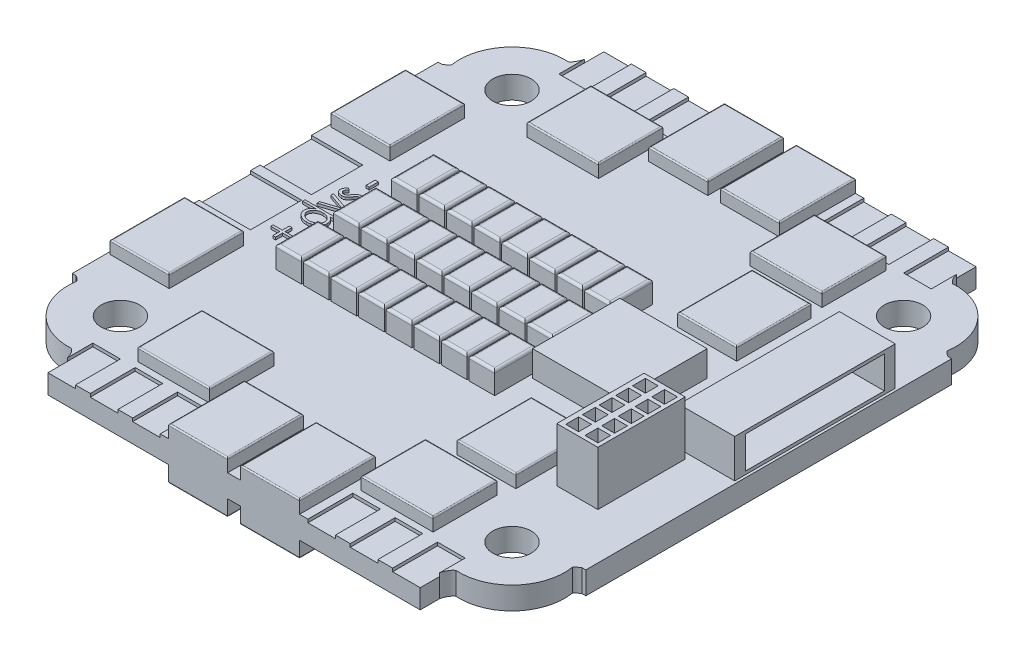
SolidWorks part; units mm, degrees
ref_plane "Ön Düzlem" through (0, 0, 0) normal (0, 0, 1) x (1, 0, 0)
ref_plane "Üst Düzlem" through (0, 0, 0) normal (0, 1, 0) x (1, 0, 0)
ref_plane "Sağ Düzlem" through (0, 0, 0) normal (1, 0, 0) x (0, 0, -1)
sketch "Çizim1" plane through (0, 0, 0) normal (0, 1, 0) x (1, 0, 0)
  line L0 (0, 44.0782) -> (0, -46.2011) construction
  line L1 (20, -21.65) -> (-20, -21.65)
  line L2 (20, -21.65) -> (20, 21.65)
  line L3 (20, 21.65) -> (-20, 21.65)
  line L4 (-20, -21.65) -> (-20, 21.65)
  line L5 (20, -21.65) -> (-20, 21.65) construction
  line L6 (20, 21.65) -> (-20, -21.65) construction
  line L7 (-44.1341, 0) -> (49.6089, 0) construction
  line L9 (15.25, -15.25) -> (-15.25, -15.25) construction
  line L10 (15.25, -15.25) -> (15.25, 15.25) construction
  line L11 (15.25, 15.25) -> (-15.25, 15.25) construction
  line L12 (-15.25, -15.25) -> (-15.25, 15.25) construction
  line L13 (15.25, -15.25) -> (-15.25, 15.25) construction
  line L14 (15.25, 15.25) -> (-15.25, -15.25) construction
  point P0 (0, 0)
  point P10 (0, 0)
  dimension "D1" = 40
  dimension "D2" = 43.3
  dimension "D3" = 30.5
  dimension "D4" = 30.5
extrude "Yükseklik-Ekstrüzyon1" add sketch "Çizim1" along normal blind 1.75
sketch "Çizim2" plane through (0, 0, 0) normal (0, 1, 0) x (1, 0, 0)
  line L1 (15.25, -15.25) -> (-15.25, -15.25) construction
  line L2 (15.25, -15.25) -> (15.25, 15.25) construction
  line L3 (15.25, 15.25) -> (-15.25, 15.25) construction
  line L4 (-15.25, -15.25) -> (-15.25, 15.25) construction
  line L5 (15.25, -15.25) -> (-15.25, 15.25) construction
  line L6 (15.25, 15.25) -> (-15.25, -15.25) construction
  circle A0 centre (-15.25, 15.25) radius 1.5
  circle A1 centre (15.25, 15.25) radius 1.5
  circle A2 centre (15.25, -15.25) radius 1.5
  circle A3 centre (-15.25, -15.25) radius 1.5
  point P0 (0, 0)
  dimension "D1" = 30.5
  dimension "D2" = 30.5
extrude "Kes-Ekstrüzyon1" cut sketch "Çizim2" along normal blind 1.75
sketch "Çizim3" plane through (0, 0, 0) normal (0, 1, 0) x (1, 0, 0)
  line L0 (-19.297, 14.593) -> (-19.4339, 14.3985) construction
  line L1 (-19.4339, 14.3985) -> (-19.7178, 14.25) construction
  line L2 (-20, 21.65) -> (-20, -21.65) construction
  line L3 (-19.7178, 14.25) -> (-20, 14.25)
  line L4 (-20, 21.65) -> (-20, 13.5542) construction
  line L5 (-20, 14.25) -> (-20, 21.65)
  line L6 (-20, 21.65) -> (-14.5, 21.65)
  line L7 (20, 21.65) -> (-20, 21.65) construction
  line L8 (-14.5, 21.65) -> (-14.5, 20.1378)
  line L9 (-14.9713, 19.3405) -> (-14.7537, 19.4813) construction
  line L10 (-14.7537, 19.4813) -> (-14.5714, 19.809) construction
  line L11 (-14.5714, 19.809) -> (-14.5, 20.1378) construction
  line L12 (20, 21.65) -> (14.5, 21.65)
  line L13 (14.5, 21.65) -> (14.5, 20.1378)
  line L14 (14.9713, 19.3405) -> (14.7537, 19.4813) construction
  line L15 (0, 29.2521) -> (0, -30.7082) construction
  line L16 (-36.8808, 0) -> (40.0068, 0) construction
  line L17 (14.7537, 19.4813) -> (14.5714, 19.809) construction
  line L18 (14.5714, 19.809) -> (14.5, 20.1378) construction
  line L19 (20, 14.25) -> (20, 21.65)
  line L20 (19.7178, 14.25) -> (20, 14.25)
  line L21 (19.297, 14.593) -> (19.4339, 14.3985) construction
  line L22 (19.4339, 14.3985) -> (19.7178, 14.25) construction
  line L23 (14.9713, -19.3405) -> (14.7537, -19.4813) construction
  line L24 (14.7537, -19.4813) -> (14.5714, -19.809) construction
  line L25 (14.5714, -19.809) -> (14.5, -20.1378) construction
  line L26 (19.297, -14.593) -> (19.4339, -14.3985) construction
  line L27 (19.4339, -14.3985) -> (19.7178, -14.25) construction
  line L28 (19.7178, -14.25) -> (20, -14.25)
  line L29 (20, -14.25) -> (20, -21.65)
  line L30 (20, -21.65) -> (14.5, -21.65)
  line L31 (14.5, 18.3234) -> (-14.5, 18.3234) construction
  line L32 (14.5, -21.65) -> (14.5, -20.1378)
  line L33 (14.5, 18.3234) -> (14.5, 24.9766) construction
  line L34 (-20, -21.65) -> (-14.5, -21.65)
  line L35 (-14.5, -21.65) -> (-14.5, -20.1378)
  line L36 (-14.9713, -19.3405) -> (-14.7537, -19.4813) construction
  line L37 (-14.7537, -19.4813) -> (-14.5714, -19.809) construction
  line L38 (-14.5714, -19.809) -> (-14.5, -20.1378) construction
  line L39 (-20, -14.25) -> (-20, -21.65)
  line L40 (-19.7178, -14.25) -> (-20, -14.25)
  line L41 (-19.297, -14.593) -> (-19.4339, -14.3985) construction
  line L42 (-19.4339, -14.3985) -> (-19.7178, -14.25) construction
  line L48 (14.5, 24.9766) -> (-14.5, 24.9766) construction
  line L49 (-14.5, 18.3234) -> (-14.5, 24.9766) construction
  line L50 (14.5, 18.3234) -> (-14.5, 24.9766) construction
  line L51 (14.5, 24.9766) -> (-14.5, 18.3234) construction
  line L52 (-14.1712, -14.25) -> (-25.8288, -14.25) construction
  line L53 (-14.1712, -14.25) -> (-14.1712, 14.25) construction
  line L54 (-14.1712, 14.25) -> (-25.8288, 14.25) construction
  line L55 (-25.8288, -14.25) -> (-25.8288, 14.25) construction
  line L56 (-14.1712, -14.25) -> (-25.8288, 14.25) construction
  line L57 (-14.1712, 14.25) -> (-25.8288, -14.25) construction
  arc A0 (14.9713, 19.3405) -> (19.297, 14.593) centre (15.25, 15.25) cw
  circle A1 centre (0, 0) radius 6.746 construction
  arc A2 (14.9713, -19.3405) -> (19.297, -14.593) centre (15.25, -15.25) ccw
  arc A3 (-14.9713, -19.3405) -> (-19.297, -14.593) centre (-15.25, -15.25) cw
  arc A5 (-14.9713, 19.3405) -> (-19.297, 14.593) centre (-15.25, 15.25) ccw
  spline S0 degree 2 poles (-19.297, 14.593) (-19.4339, 14.3985) (-19.7178, 14.25) knots 0 0 0 1 1 1
  spline S1 degree 3 poles (-14.9713, 19.3405) (-14.7537, 19.4813) (-14.5714, 19.809) (-14.5, 20.1378) knots 0 0 0 0 1 1 1 1
  spline S2 degree 3 poles (14.9713, 19.3405) (14.7537, 19.4813) (14.5714, 19.809) (14.5, 20.1378) knots 0 0 0 0 1 1 1 1
  spline S3 degree 2 poles (19.297, 14.593) (19.4339, 14.3985) (19.7178, 14.25) knots 0 0 0 1 1 1
  spline S4 degree 3 poles (14.9713, -19.3405) (14.7537, -19.4813) (14.5714, -19.809) (14.5, -20.1378) knots 0 0 0 0 1 1 1 1
  spline S5 degree 2 poles (19.297, -14.593) (19.4339, -14.3985) (19.7178, -14.25) knots 0 0 0 1 1 1
  spline S6 degree 3 poles (-14.9713, -19.3405) (-14.7537, -19.4813) (-14.5714, -19.809) (-14.5, -20.1378) knots 0 0 0 0 1 1 1 1
  spline S7 degree 2 poles (-19.297, -14.593) (-19.4339, -14.3985) (-19.7178, -14.25) knots 0 0 0 1 1 1
  point P43 (0, 21.65)
  point P61 (-20, 0)
  dimension "D1" = 29
  dimension "D2" = 28.5
extrude "Kes-Ekstrüzyon4" cut sketch "Çizim3" along normal blind 1.75
sketch "Çizim5" plane through (0, 0, 0) normal (0, 1, 0) x (1, 0, 0)
  line L0 (0, 30.9186) -> (0, -32.6939) construction
  line L1 (-49.0396, 0) -> (40.1136, 0) construction
  line L2 (-10.125, 21.65) -> (-10.125, 17.2464) construction
  line L3 (-14.5, 21.65) -> (-5.75, 21.65) construction
  line L4 (-14.5, 21.65) -> (-14.5, 18.15) construction
  line L5 (-14.5, 18.15) -> (-5.75, 18.15) construction
  line L6 (-5.75, 21.65) -> (-5.75, 18.15) construction
  line L7 (-14.5, 21.65) -> (-12.3523, 21.65)
  line L8 (-14.5, 21.65) -> (-14.5, 18.15)
  line L9 (-14.5, 18.15) -> (-12.3523, 18.15)
  line L10 (-12.3523, 21.65) -> (-12.3523, 18.15)
  line L11 (-5.75, 18.15) -> (-7.8977, 18.15)
  line L12 (-5.75, 21.65) -> (-5.75, 18.15)
  line L13 (-5.75, 21.65) -> (-7.8977, 21.65)
  line L14 (-7.8977, 21.65) -> (-7.8977, 18.15)
  line L15 (-5.75, 19.9) -> (-14.5, 19.9) construction
  line L16 (9.05, 21.65) -> (11.2, 18.15) construction
  line L17 (-9.05, 18.15) -> (-11.2, 18.15)
  line L18 (-9.05, 18.15) -> (-9.05, 21.65)
  line L19 (-9.05, 21.65) -> (-11.2, 21.65)
  line L20 (-11.2, 18.15) -> (-11.2, 21.65)
  line L21 (-9.05, 18.15) -> (-11.2, 21.65) construction
  line L22 (-9.05, 21.65) -> (-11.2, 18.15) construction
  line L23 (9.05, 18.15) -> (11.2, 21.65) construction
  line L24 (5.75, 19.9) -> (14.5, 19.9) construction
  line L25 (5.75, 21.65) -> (5.75, 18.15) construction
  line L26 (14.5, 18.15) -> (5.75, 18.15) construction
  line L27 (14.5, 21.65) -> (14.5, 18.15) construction
  line L28 (14.5, 21.65) -> (5.75, 21.65) construction
  line L29 (10.125, 21.65) -> (10.125, 17.2464) construction
  line L30 (11.2, 18.15) -> (11.2, 21.65)
  line L31 (9.05, 21.65) -> (11.2, 21.65)
  line L32 (9.05, 18.15) -> (9.05, 21.65)
  line L33 (9.05, 18.15) -> (11.2, 18.15)
  line L34 (7.8977, 21.65) -> (7.8977, 18.15)
  line L35 (5.75, 21.65) -> (7.8977, 21.65)
  line L36 (5.75, 21.65) -> (5.75, 18.15)
  line L37 (5.75, 18.15) -> (7.8977, 18.15)
  line L38 (12.3523, 21.65) -> (12.3523, 18.15)
  line L39 (14.5, 18.15) -> (12.3523, 18.15)
  line L40 (14.5, 21.65) -> (14.5, 18.15)
  line L41 (14.5, 21.65) -> (12.3523, 21.65)
  line L42 (10.125, -21.65) -> (10.125, -17.2464) construction
  line L43 (14.5, -21.65) -> (5.75, -21.65) construction
  line L44 (14.5, -21.65) -> (14.5, -18.15) construction
  line L45 (14.5, -18.15) -> (5.75, -18.15) construction
  line L46 (5.75, -21.65) -> (5.75, -18.15) construction
  line L47 (5.75, -19.9) -> (14.5, -19.9) construction
  line L48 (9.05, -18.15) -> (11.2, -21.65) construction
  line L49 (-9.05, -21.65) -> (-11.2, -18.15) construction
  line L50 (-9.05, -18.15) -> (-11.2, -21.65) construction
  line L51 (9.05, -21.65) -> (11.2, -18.15) construction
  line L52 (-5.75, -19.9) -> (-14.5, -19.9) construction
  line L53 (-5.75, -21.65) -> (-5.75, -18.15) construction
  line L54 (-14.5, -18.15) -> (-5.75, -18.15) construction
  line L55 (-14.5, -21.65) -> (-14.5, -18.15) construction
  line L56 (-14.5, -21.65) -> (-5.75, -21.65) construction
  line L57 (-10.125, -21.65) -> (-10.125, -17.2464) construction
  line L58 (14.5, -21.65) -> (12.3523, -21.65)
  line L59 (14.5, -21.65) -> (14.5, -18.15)
  line L60 (14.5, -18.15) -> (12.3523, -18.15)
  line L61 (12.3523, -21.65) -> (12.3523, -18.15)
  line L62 (5.75, -18.15) -> (7.8977, -18.15)
  line L63 (5.75, -21.65) -> (5.75, -18.15)
  line L64 (5.75, -21.65) -> (7.8977, -21.65)
  line L65 (7.8977, -21.65) -> (7.8977, -18.15)
  line L66 (9.05, -18.15) -> (11.2, -18.15)
  line L67 (9.05, -18.15) -> (9.05, -21.65)
  line L68 (9.05, -21.65) -> (11.2, -21.65)
  line L69 (11.2, -18.15) -> (11.2, -21.65)
  line L70 (-11.2, -18.15) -> (-11.2, -21.65)
  line L71 (-9.05, -21.65) -> (-11.2, -21.65)
  line L72 (-9.05, -18.15) -> (-9.05, -21.65)
  line L73 (-9.05, -18.15) -> (-11.2, -18.15)
  line L74 (-7.8977, -21.65) -> (-7.8977, -18.15)
  line L75 (-5.75, -21.65) -> (-7.8977, -21.65)
  line L76 (-5.75, -21.65) -> (-5.75, -18.15)
  line L77 (-5.75, -18.15) -> (-7.8977, -18.15)
  line L78 (-12.3523, -21.65) -> (-12.3523, -18.15)
  line L79 (-14.5, -18.15) -> (-12.3523, -18.15)
  line L80 (-14.5, -21.65) -> (-14.5, -18.15)
  line L81 (-14.5, -21.65) -> (-12.3523, -21.65)
  point P18 (-10.125, 19.9)
  point P39 (10.125, 19.9)
  point P72 (10.125, -19.9)
  point P73 (-10.125, -19.9)
  dimension "D1" = 8.75
  dimension "D2" = 3.5
  dimension "D3" = 2.15
extrude "Kes-Ekstrüzyon5" cut sketch "Çizim5" along normal blind 1 from offset 1.5
sketch "Çizim6" plane through (0, 0, 0) normal (0, 1, 0) x (1, 0, 0)
  line L0 (-37.3382, 0) -> (45.0839, 0) construction
  line L1 (-20, 14.25) -> (-20, -14.25) construction
  line L2 (-15.9, -4.375) -> (-20, -4.375) construction
  line L3 (-15.9, -4.375) -> (-15.9, 4.375) construction
  line L4 (-15.9, 4.375) -> (-20, 4.375) construction
  line L5 (-20, -4.375) -> (-20, 4.375) construction
  line L6 (-15.9, -4.375) -> (-20, 4.375) construction
  line L7 (-15.9, 4.375) -> (-20, -4.375) construction
  line L8 (-20, -4.375) -> (-20, -0.375)
  line L9 (-20, 4.375) -> (-16, 4.375)
  line L10 (-20, 4.375) -> (-20, 0.375)
  line L11 (-20, 0.375) -> (-16, 0.375)
  line L12 (-16, 4.375) -> (-16, 0.375)
  line L13 (-20, -4.375) -> (-16, -4.375)
  line L14 (-16, -4.375) -> (-16, -0.375)
  line L15 (-20, -0.375) -> (-16, -0.375)
  point P3 (-17.95, 0)
  dimension "D1" = 8.75
  dimension "D2" = 4.1
  dimension "D3" = 4
  dimension "D4" = 4
extrude "Kes-Ekstrüzyon7" cut sketch "Çizim6" along normal blind 1 from offset 1.5
sketch "Çizim7" plane through (0, 0, 0) normal (0, 1, 0) x (1, 0, 0)
  line L0 (12, 0) -> (-20, 0) construction
  line L1 (-20, 14.25) -> (-20, 4.375) construction
  line L2 (-15.2, -11.5) -> (-20, -11.5) construction
  line L3 (-15.2, -11.5) -> (-15.2, 11.5) construction
  line L4 (-15.2, 11.5) -> (-20, 11.5) construction
  line L5 (-20, -11.5) -> (-20, 11.5) construction
  line L6 (-15.2, -11.5) -> (-20, 11.5) construction
  line L7 (-15.2, 11.5) -> (-20, -11.5) construction
  line L8 (-19.8, 11.9264) -> (-19.8, -13.8708) construction
  line L9 (-19.8, -11.5) -> (-15.2, -11.5)
  line L10 (-19.8, 11.5) -> (-15.2, 11.5)
  line L11 (-19.8, 11.5) -> (-19.8, 5.7)
  line L12 (-19.8, 5.7) -> (-15.2, 5.7)
  line L13 (-15.2, 11.5) -> (-15.2, 5.7)
  line L14 (-15.2, -11.5) -> (-15.2, -5.7)
  line L15 (-19.8, -11.5) -> (-19.8, -5.7)
  line L16 (-19.8, -5.7) -> (-15.2, -5.7)
  line L17 (12, 23.8694) -> (12, -27.9826) construction
  line L18 (20, -14.25) -> (20, 14.25) construction
  line L19 (-20, 21.0492) -> (-20, -26.7007) construction
  line L20 (-4, 16.02) -> (-4, -18.6893) construction
  line L21 (11.8, -11.5) -> (11.8, -5.7)
  line L22 (11.8, -11.5) -> (7.2, -11.5)
  line L23 (7.2, -11.5) -> (7.2, -5.7)
  line L24 (11.8, -5.7) -> (7.2, -5.7)
  line L25 (11.8, 11.5) -> (11.8, 5.7)
  line L26 (11.8, 5.7) -> (7.2, 5.7)
  line L27 (7.2, 11.5) -> (7.2, 5.7)
  line L28 (11.8, 11.5) -> (7.2, 11.5)
  point P3 (-17.6, 0)
  point P16 (-17.5, -11.5)
  point P19 (-17.5, -5.7)
  dimension "D1" = 23
  dimension "D2" = 0.2
  dimension "D3" = 5.8
  dimension "D4" = 8
extrude "Yükseklik-Ekstrüzyon2" add sketch "Çizim7" along normal blind 2.75 and the other way blind 1.25
sketch "Çizim9" plane through (0, 0, 0) normal (0, 1, 0) x (1, 0, 0)
  line L0 (11.8, 15.4181) -> (11.8, -15.0147) construction
  line L1 (-13.0732, 0) -> (28.7719, 0) construction
  line L2 (-13.0732, 3.4) -> (30.1552, 3.4) construction
  line L4 (11.8, 3.4) -> (5, 3.4)
  line L5 (11.8, 3.4) -> (11.8, -3.4)
  line L6 (11.8, -3.4) -> (5, -3.4)
  line L7 (5, 3.4) -> (5, -3.4)
  dimension "D1" = 3.4
  dimension "D2" = 6.8
  dimension "D3" = 6.8
extrude "Yükseklik-Ekstrüzyon3" add sketch "Çizim9" along normal blind 3.75
sketch "Çizim10" plane through (0, 0, 0) normal (0, 1, 0) x (1, 0, 0)
  line L0 (0, 23.2569) -> (0, -24.4096) construction
  line L1 (5.75, 21.65) -> (-5.75, 21.65) construction
  line L2 (5.1, 15.75) -> (-5.1, 15.75) construction
  line L3 (5.1, 15.75) -> (5.1, 21.65) construction
  line L4 (5.1, 21.65) -> (-5.1, 21.65) construction
  line L5 (-5.1, 15.75) -> (-5.1, 21.65) construction
  line L6 (5.1, 15.75) -> (-5.1, 21.65) construction
  line L7 (5.1, 21.65) -> (-5.1, 15.75) construction
  line L8 (-5.1, 15.75) -> (-0.5021, 15.75)
  line L9 (5.1, 21.65) -> (0.5021, 21.65)
  line L10 (5.1, 21.65) -> (5.1, 15.75)
  line L11 (5.1, 15.75) -> (0.5021, 15.75)
  line L12 (0.5021, 21.65) -> (0.5021, 15.75)
  line L13 (-0.5021, 21.65) -> (-0.5021, 15.75)
  line L14 (-5.1, 21.65) -> (-0.5021, 21.65)
  line L15 (-5.1, 21.65) -> (-5.1, 15.75)
  line L16 (-34.7799, 0) -> (34.025, 0) construction
  line L17 (-17.6922, 17.65) -> (20.1896, 17.65) construction
  line L18 (-12.3523, 18.15) -> (-14.5, 18.15) construction
  line L19 (-17.6922, 15.15) -> (18.3088, 15.15) construction
  line L20 (11.5, 17.65) -> (11.5, 12.65)
  line L21 (11.5, 12.65) -> (-11.5, 12.65) construction
  line L22 (11.5, 12.65) -> (11.5, 17.65) construction
  line L23 (11.5, 17.65) -> (-11.5, 17.65) construction
  line L24 (-11.5, 12.65) -> (-11.5, 17.65) construction
  line L25 (11.5, 12.65) -> (-11.5, 17.65) construction
  line L26 (11.5, 17.65) -> (-11.5, 12.65) construction
  line L27 (-11.5, 17.65) -> (-5.9038, 17.65)
  line L28 (-11.5, 17.65) -> (-11.5, 12.65)
  line L29 (-11.5, 12.65) -> (-5.9038, 12.65)
  line L30 (-5.9038, 17.65) -> (-5.9038, 12.65)
  line L31 (11.5, 17.65) -> (5.9038, 17.65)
  line L32 (5.9038, 17.65) -> (5.9038, 12.65)
  line L33 (11.5, 12.65) -> (5.9038, 12.65)
  line L34 (11.5, -17.65) -> (-11.5, -12.65) construction
  line L35 (11.5, -12.65) -> (-11.5, -17.65) construction
  line L36 (-11.5, -12.65) -> (-11.5, -17.65) construction
  line L37 (11.5, -17.65) -> (-11.5, -17.65) construction
  line L38 (11.5, -12.65) -> (11.5, -17.65) construction
  line L39 (11.5, -12.65) -> (-11.5, -12.65) construction
  line L40 (-17.6922, -15.15) -> (18.3088, -15.15) construction
  line L41 (-17.6922, -17.65) -> (20.1896, -17.65) construction
  line L42 (5.1, -21.65) -> (-5.1, -15.75) construction
  line L43 (5.1, -15.75) -> (-5.1, -21.65) construction
  line L44 (-5.1, -15.75) -> (-5.1, -21.65) construction
  line L45 (5.1, -21.65) -> (-5.1, -21.65) construction
  line L46 (5.1, -15.75) -> (5.1, -21.65) construction
  line L47 (5.1, -15.75) -> (-5.1, -15.75) construction
  line L48 (0, -23.2569) -> (0, 24.4096) construction
  line L49 (11.5, -12.65) -> (5.9038, -12.65)
  line L50 (5.9038, -17.65) -> (5.9038, -12.65)
  line L51 (11.5, -17.65) -> (5.9038, -17.65)
  line L52 (-5.9038, -17.65) -> (-5.9038, -12.65)
  line L53 (-11.5, -12.65) -> (-5.9038, -12.65)
  line L54 (-11.5, -17.65) -> (-11.5, -12.65)
  line L55 (-11.5, -17.65) -> (-5.9038, -17.65)
  line L56 (11.5, -17.65) -> (11.5, -12.65)
  line L57 (-5.1, -21.65) -> (-5.1, -15.75)
  line L58 (-5.1, -21.65) -> (-0.5021, -21.65)
  line L59 (-0.5021, -21.65) -> (-0.5021, -15.75)
  line L60 (0.5021, -21.65) -> (0.5021, -15.75)
  line L61 (5.1, -15.75) -> (0.5021, -15.75)
  line L62 (5.1, -21.65) -> (5.1, -15.75)
  line L63 (5.1, -21.65) -> (0.5021, -21.65)
  line L64 (-5.1, -15.75) -> (-0.5021, -15.75)
  line L65 (-5.7307, 22.4988) -> (4.1432, 22.4988) construction
  point P3 (0, 18.7)
  point P22 (0, 15.15)
  point P53 (0, -15.15)
  point P54 (0, -18.7)
  dimension "D1" = 10.2
  dimension "D2" = 5.9
  dimension "D3" = 0.5
  dimension "D4" = 2.5
  dimension "D5" = 23
  dimension "D6" = 5.5962
  dimension "D7" = 0.8488
extrude "Yükseklik-Ekstrüzyon4" add sketch "Çizim10" along normal blind 2.75 and the other way blind 1.25
sketch "Çizim11" plane through (0, 0, 0) normal (0, 1, 0) x (1, 0, 0)
  line L0 (-37.3419, -0.2797) -> (45.0802, -0.2797) construction
  line L1 (-15.9037, -4.6547) -> (-20.0037, -4.6547) construction
  line L2 (-15.9037, -4.6547) -> (-15.9037, 4.0953) construction
  line L3 (-15.9037, 4.0953) -> (-20.0037, 4.0953) construction
  line L4 (-20.0037, -4.6547) -> (-20.0037, 4.0953) construction
  line L5 (-15.9037, -4.6547) -> (-20.0037, 4.0953) construction
  line L6 (-15.9037, 4.0953) -> (-20.0037, -4.6547) construction
  line L7 (-20.0037, -4.6547) -> (-20.0037, -0.6547)
  line L8 (-20.0037, 4.0953) -> (-16.0037, 4.0953)
  line L9 (-20.0037, 4.0953) -> (-20.0037, 0.0953)
  line L10 (-20.0037, 0.0953) -> (-16.0037, 0.0953)
  line L11 (-16.0037, 4.0953) -> (-16.0037, 0.0953)
  line L12 (-20.0037, -4.6547) -> (-16.0037, -4.6547)
  line L13 (-16.0037, -4.6547) -> (-16.0037, -0.6547)
  line L14 (-20.0037, -0.6547) -> (-16.0037, -0.6547)
  point P2 (-17.9537, -0.2797)
  dimension "D1" = 8.75
  dimension "D2" = 4.1
  dimension "D3" = 4
  dimension "D4" = 4
extrude "Kes-Ekstrüzyon8" cut sketch "Çizim11" along normal blind 0.5
sketch "Çizim12" plane through (0, 0, 0) normal (0, 1, 0) x (1, 0, 0)
  line L0 (20, 14.25) -> (29.4504, 14.25) construction
  line L1 (32.1594, 10.05) -> (-8.1295, 10.05) construction
  line L2 (19.8, 11.0054) -> (19.8, -21.7671) construction
  line L3 (20, -14.25) -> (20, 14.25) construction
  line L5 (19.8, 10.05) -> (15.45, 10.05)
  line L6 (19.8, 10.05) -> (19.8, -2.45)
  line L7 (19.8, -2.45) -> (15.45, -2.45)
  line L8 (15.45, 10.05) -> (15.45, -2.45)
  dimension "D1" = 4.2
  dimension "D2" = 0.2
  dimension "D3" = 12.5
  dimension "D4" = 4.35
extrude "Yükseklik-Ekstrüzyon5" add sketch "Çizim12" along normal blind 3 from surface starting at face at (-1.6364, 1.75, 0)
ref_plane "Düzlem1" through (29.8, 0, 0) normal (1, 0, 0) x (0, 0, -1)
sketch "Çizim13" plane through (29.8, 0, 0) normal (1, 0, 0) x (0, 0, -1)
  line L0 (3.8, 4.75) -> (3.8, 1.086) construction
  line L1 (10.05, 4.75) -> (-2.45, 4.75) construction
  line L2 (-2.45, 3.25) -> (10.05, 3.25) construction
  line L3 (-2.45, 4.75) -> (-2.45, 1.75) construction
  line L4 (10.05, 4.75) -> (10.05, 1.75) construction
  line L6 (9.2, 2) -> (-1.6, 2)
  line L7 (9.2, 2) -> (9.2, 4.5)
  line L8 (9.2, 4.5) -> (-1.6, 4.5)
  line L9 (-1.6, 2) -> (-1.6, 4.5)
  line L10 (9.2, 2) -> (-1.6, 4.5) construction
  line L11 (9.2, 4.5) -> (-1.6, 2) construction
  point P10 (3.8, 3.25)
  dimension "D1" = 10.8
  dimension "D2" = 2.5
extrude "Kes-Ekstrüzyon9" cut sketch "Çizim13" against normal blind 13
sketch "Çizim14" plane through (0, 0, 0) normal (0, 1, 0) x (1, 0, 0)
  line L0 (16.4, 0.4899) -> (16.4, -23.3722) construction
  line L1 (20, -14.25) -> (20, 14.25) construction
  line L2 (20, -2.9107) -> (10.3037, -2.9107) construction
  line L4 (16.4, -2.9107) -> (13.2, -2.9107)
  line L5 (16.4, -2.9107) -> (16.4, -9.7107)
  line L6 (16.4, -9.7107) -> (13.2, -9.7107)
  line L7 (13.2, -2.9107) -> (13.2, -9.7107)
  dimension "D1" = 3.6
  dimension "D2" = 3.2
  dimension "D3" = 6.8
extrude "Yükseklik-Ekstrüzyon6" add sketch "Çizim14" along normal blind 4.2 from surface starting at face at (17.625, 1.75, -3.8)
ref_plane "Düzlem2" through (0, 5.95, 0) normal (0, 1, 0) x (1, 0, 0)
sketch "Çizim15" plane through (0, 5.95, 0) normal (0, 1, 0) x (1, 0, 0)
  line L0 (14.8, -2.9107) -> (14.8, -11.4983) construction
  line L1 (13.2, -2.9107) -> (16.4, -2.9107) construction
  line L2 (13.2, -6.3107) -> (18.1949, -6.3107) construction
  line L3 (13.2, -9.7107) -> (13.2, -2.9107) construction
  line L4 (17.215, -3.2107) -> (12.1271, -3.2107) construction
  line L5 (13.2, -2.9107) -> (16.4, -2.9107) construction
  line L6 (14.8, -2.9107) -> (16.4, -2.9107) construction
  line L7 (15.6, -2.9107) -> (15.6, -10.0902) construction
  line L8 (15.1, -2.7946) -> (15.1, -11.569) construction
  line L9 (16.1, -2.7946) -> (16.1, -11.569) construction
  line L10 (13.6, -4.213) -> (14.6, -4.213)
  line L11 (15.1, -3.2107) -> (16.1, -3.2107)
  line L12 (15.1, -3.2107) -> (15.1, -4.213)
  line L13 (15.1, -4.213) -> (16.1, -4.213)
  line L14 (16.1, -3.2107) -> (16.1, -4.213)
  line L15 (14.6, -3.2107) -> (14.6, -4.213)
  line L16 (13.6, -3.2107) -> (14.6, -3.2107)
  line L17 (13.6, -3.2107) -> (13.6, -4.213)
  line L18 (13.6, -5.513) -> (14.6, -5.513)
  line L19 (14.6, -4.5107) -> (14.6, -5.513)
  line L20 (13.6, -4.5107) -> (14.6, -4.5107)
  line L21 (13.6, -4.5107) -> (13.6, -5.513)
  line L22 (13.6, -6.813) -> (14.6, -6.813)
  line L23 (14.6, -5.8107) -> (14.6, -6.813)
  line L24 (13.6, -5.8107) -> (14.6, -5.8107)
  line L25 (13.6, -5.8107) -> (13.6, -6.813)
  line L26 (13.6, -8.113) -> (14.6, -8.113)
  line L27 (14.6, -7.1107) -> (14.6, -8.113)
  line L28 (13.6, -7.1107) -> (14.6, -7.1107)
  line L29 (13.6, -7.1107) -> (13.6, -8.113)
  line L30 (13.6, -9.413) -> (14.6, -9.413)
  line L31 (14.6, -8.4107) -> (14.6, -9.413)
  line L32 (13.6, -8.4107) -> (14.6, -8.4107)
  line L33 (13.6, -8.4107) -> (13.6, -9.413)
  line L34 (15.1, -5.513) -> (16.1, -5.513)
  line L35 (16.1, -4.5107) -> (16.1, -5.513)
  line L36 (15.1, -4.5107) -> (16.1, -4.5107)
  line L37 (15.1, -4.5107) -> (15.1, -5.513)
  line L38 (15.1, -6.813) -> (16.1, -6.813)
  line L39 (16.1, -5.8107) -> (16.1, -6.813)
  line L40 (15.1, -5.8107) -> (16.1, -5.8107)
  line L41 (15.1, -5.8107) -> (15.1, -6.813)
  line L42 (15.1, -8.113) -> (16.1, -8.113)
  line L43 (16.1, -7.1107) -> (16.1, -8.113)
  line L44 (15.1, -7.1107) -> (16.1, -7.1107)
  line L45 (15.1, -7.1107) -> (15.1, -8.113)
  line L46 (15.1, -9.413) -> (16.1, -9.413)
  line L47 (16.1, -8.4107) -> (16.1, -9.413)
  line L48 (15.1, -8.4107) -> (16.1, -8.4107)
  line L49 (15.1, -8.4107) -> (15.1, -9.413)
  point P18 (15.6, -3.6747)
  dimension "D1" = 0.3
  dimension "D2" = 2
  dimension "D3" = 5
extrude "Kes-Ekstrüzyon10" cut sketch "Çizim15" against normal blind 3
sketch "Çizim16" plane through (0, 0, 0) normal (0, 1, 0) x (1, 0, 0)
  line L0 (-12.5, 22.9111) -> (-12.5, -24.352) construction
  line L1 (-20, 0.375) -> (-20, -0.375) construction
  line L2 (-30.7148, 0) -> (26.2314, 0) construction
  line L3 (-26.6801, 6.25) -> (27.3842, 6.25) construction
  line L4 (-4.2014, 6.25) -> (-4.2014, 0) construction
  line L5 (-12.5, 6.25) -> (4.7, 6.25) construction
  line L6 (-12.5, 6.25) -> (-12.5, -6.25) construction
  line L7 (-12.5, -6.25) -> (4.7, -6.25) construction
  line L8 (4.7, 6.25) -> (4.7, -6.25) construction
  line L9 (-13.8057, 2.95) -> (8.3849, 2.95) construction
  line L10 (0.55, 6.25) -> (0.55, 2.95)
  line L11 (4.7, 6.25) -> (2.7, 6.25)
  line L12 (4.7, 6.25) -> (4.7, 2.95)
  line L13 (4.7, 2.95) -> (2.7, 2.95)
  line L14 (2.7, 6.25) -> (2.7, 2.95)
  line L15 (2.55, 6.25) -> (0.55, 6.25)
  line L16 (2.55, 6.25) -> (2.55, 2.95)
  line L17 (2.55, 2.95) -> (0.55, 2.95)
  line L18 (-1.6, 6.25) -> (-1.6, 2.95)
  line L19 (0.4, 6.25) -> (-1.6, 6.25)
  line L20 (0.4, 6.25) -> (0.4, 2.95)
  line L21 (0.4, 2.95) -> (-1.6, 2.95)
  line L22 (-3.75, 6.25) -> (-3.75, 2.95)
  line L23 (-1.75, 6.25) -> (-3.75, 6.25)
  line L24 (-1.75, 6.25) -> (-1.75, 2.95)
  line L25 (-1.75, 2.95) -> (-3.75, 2.95)
  line L26 (-5.9, 6.25) -> (-5.9, 2.95)
  line L27 (-3.9, 6.25) -> (-5.9, 6.25)
  line L28 (-3.9, 6.25) -> (-3.9, 2.95)
  line L29 (-3.9, 2.95) -> (-5.9, 2.95)
  line L30 (-8.05, 6.25) -> (-8.05, 2.95)
  line L31 (-6.05, 6.25) -> (-8.05, 6.25)
  line L32 (-6.05, 6.25) -> (-6.05, 2.95)
  line L33 (-6.05, 2.95) -> (-8.05, 2.95)
  line L34 (-10.2, 6.25) -> (-10.2, 2.95)
  line L35 (-8.2, 6.25) -> (-10.2, 6.25)
  line L36 (-8.2, 6.25) -> (-8.2, 2.95)
  line L37 (-8.2, 2.95) -> (-10.2, 2.95)
  line L38 (-12.35, 6.25) -> (-12.35, 2.95)
  line L39 (-10.35, 6.25) -> (-12.35, 6.25)
  line L40 (-10.35, 6.25) -> (-10.35, 2.95)
  line L41 (-10.35, 2.95) -> (-12.35, 2.95)
  line L42 (0.55, 1.75) -> (0.55, -1.55)
  line L43 (2.55, 1.75) -> (0.55, 1.75)
  line L44 (2.55, 1.75) -> (2.55, -1.55)
  line L45 (2.55, -1.55) -> (0.55, -1.55)
  line L46 (-1.6, 1.75) -> (-1.6, -1.55)
  line L47 (0.4, 1.75) -> (-1.6, 1.75)
  line L48 (0.4, 1.75) -> (0.4, -1.55)
  line L49 (0.4, -1.55) -> (-1.6, -1.55)
  line L50 (-3.75, 1.75) -> (-3.75, -1.55)
  line L51 (-1.75, 1.75) -> (-3.75, 1.75)
  line L52 (-1.75, 1.75) -> (-1.75, -1.55)
  line L53 (-1.75, -1.55) -> (-3.75, -1.55)
  line L54 (-5.9, 1.75) -> (-5.9, -1.55)
  line L55 (-3.9, 1.75) -> (-5.9, 1.75)
  line L56 (-3.9, 1.75) -> (-3.9, -1.55)
  line L57 (-3.9, -1.55) -> (-5.9, -1.55)
  line L58 (-8.05, 1.75) -> (-8.05, -1.55)
  line L59 (-6.05, 1.75) -> (-8.05, 1.75)
  line L60 (-6.05, 1.75) -> (-6.05, -1.55)
  line L61 (-6.05, -1.55) -> (-8.05, -1.55)
  line L62 (-10.2, 1.75) -> (-10.2, -1.55)
  line L63 (-8.2, 1.75) -> (-10.2, 1.75)
  line L64 (-8.2, 1.75) -> (-8.2, -1.55)
  line L65 (-8.2, -1.55) -> (-10.2, -1.55)
  line L66 (-12.35, 1.75) -> (-12.35, -1.55)
  line L67 (-10.35, 1.75) -> (-12.35, 1.75)
  line L68 (-10.35, 1.75) -> (-10.35, -1.55)
  line L69 (-10.35, -1.55) -> (-12.35, -1.55)
  line L70 (0.55, -2.75) -> (0.55, -6.05)
  line L71 (2.55, -2.75) -> (0.55, -2.75)
  line L72 (2.55, -2.75) -> (2.55, -6.05)
  line L73 (2.55, -6.05) -> (0.55, -6.05)
  line L74 (-1.6, -2.75) -> (-1.6, -6.05)
  line L75 (0.4, -2.75) -> (-1.6, -2.75)
  line L76 (0.4, -2.75) -> (0.4, -6.05)
  line L77 (0.4, -6.05) -> (-1.6, -6.05)
  line L78 (-3.75, -2.75) -> (-3.75, -6.05)
  line L79 (-1.75, -2.75) -> (-3.75, -2.75)
  line L80 (-1.75, -2.75) -> (-1.75, -6.05)
  line L81 (-1.75, -6.05) -> (-3.75, -6.05)
  line L82 (-5.9, -2.75) -> (-5.9, -6.05)
  line L83 (-3.9, -2.75) -> (-5.9, -2.75)
  line L84 (-3.9, -2.75) -> (-3.9, -6.05)
  line L85 (-3.9, -6.05) -> (-5.9, -6.05)
  line L86 (-8.05, -2.75) -> (-8.05, -6.05)
  line L87 (-6.05, -2.75) -> (-8.05, -2.75)
  line L88 (-6.05, -2.75) -> (-6.05, -6.05)
  line L89 (-6.05, -6.05) -> (-8.05, -6.05)
  line L90 (-10.2, -2.75) -> (-10.2, -6.05)
  line L91 (-8.2, -2.75) -> (-10.2, -2.75)
  line L92 (-8.2, -2.75) -> (-8.2, -6.05)
  line L93 (-8.2, -6.05) -> (-10.2, -6.05)
  line L94 (-12.35, -2.75) -> (-12.35, -6.05)
  line L95 (-10.35, -2.75) -> (-12.35, -2.75)
  line L96 (-10.35, -2.75) -> (-10.35, -6.05)
  line L97 (-10.35, -6.05) -> (-12.35, -6.05)
  line L98 (2.7, 1.75) -> (2.7, -1.55)
  line L99 (4.7, 1.75) -> (2.7, 1.75)
  line L100 (4.7, 1.75) -> (4.7, -1.55)
  line L101 (4.7, -1.55) -> (2.7, -1.55)
  line L102 (2.7, -2.75) -> (2.7, -6.05)
  line L103 (4.7, -2.75) -> (2.7, -2.75)
  line L104 (4.7, -2.75) -> (4.7, -6.05)
  line L105 (4.7, -6.05) -> (2.7, -6.05)
  dimension "D1" = 7.5
  dimension "D2" = 6.25
  dimension "D3" = 17.2
  dimension "D4" = 12.5
  dimension "D5" = 2
  dimension "D6" = 3.3
  dimension "D7" = 8
  dimension "D8" = 3
extrude "Yükseklik-Ekstrüzyon7" add sketch "Çizim16" along normal blind 3.45
fillet "Radyus1" radius 0.2 96 edges at (-11.35, 3.45, 6.05) (-12.35, 3.45, 4.4) (-11.35, 3.45, 2.75) (-10.35, 3.45, 4.4) (-9.2, 3.45, 6.05) (-10.2, 3.45, 4.4) (-9.2, 3.45, 2.75) (-8.2, 3.45, 4.4) (-7.05, 3.45, 6.05) (-8.05, 3.45, 4.4) (-7.05, 3.45, 2.75) (-6.05, 3.45, 4.4) (-4.9, 3.45, 6.05) (-5.9, 3.45, 4.4) (-4.9, 3.45, 2.75) (-3.9, 3.45, 4.4) (-2.75, 3.45, 6.05) (-3.75, 3.45, 4.4) (-2.75, 3.45, 2.75) (-1.75, 3.45, 4.4) (-0.6, 3.45, 6.05) (-1.6, 3.45, 4.4) (-0.6, 3.45, 2.75) (0.4, 3.45, 4.4) (1.55, 3.45, 6.05) (0.55, 3.45, 4.4) (1.55, 3.45, 2.75) (2.55, 3.45, 4.4) (3.7, 3.45, 6.05) (2.7, 3.45, 4.4) (3.7, 3.45, 2.75) (4.7, 3.45, 4.4) (3.7, 3.45, 1.55) (2.7, 3.45, -0.1) (3.7, 3.45, -1.75) (4.7, 3.45, -0.1) (1.55, 3.45, 1.55) (0.55, 3.45, -0.1) (1.55, 3.45, -1.75) (2.55, 3.45, -0.1) (-0.6, 3.45, 1.55) (-1.6, 3.45, -0.1) (-0.6, 3.45, -1.75) (0.4, 3.45, -0.1) (-2.75, 3.45, 1.55) (-3.75, 3.45, -0.1) (-2.75, 3.45, -1.75) (-1.75, 3.45, -0.1) (-4.9, 3.45, 1.55) (-5.9, 3.45, -0.1) (-4.9, 3.45, -1.75) (-3.9, 3.45, -0.1) (-7.05, 3.45, 1.55) (-8.05, 3.45, -0.1) (-7.05, 3.45, -1.75) (-6.05, 3.45, -0.1) (-9.2, 3.45, 1.55) (-10.2, 3.45, -0.1) (-9.2, 3.45, -1.75) (-8.2, 3.45, -0.1) (-11.35, 3.45, 1.55) (-12.35, 3.45, -0.1) (-11.35, 3.45, -1.75) (-10.35, 3.45, -0.1) (3.7, 3.45, -2.95) (2.7, 3.45, -4.6) (3.7, 3.45, -6.25) (4.7, 3.45, -4.6) (1.55, 3.45, -2.95) (0.55, 3.45, -4.6) (1.55, 3.45, -6.25) (2.55, 3.45, -4.6) (-0.6, 3.45, -2.95) (-1.6, 3.45, -4.6) (-0.6, 3.45, -6.25) (0.4, 3.45, -4.6) (-2.75, 3.45, -2.95) (-3.75, 3.45, -4.6) (-2.75, 3.45, -6.25) (-1.75, 3.45, -4.6) (-4.9, 3.45, -2.95) (-5.9, 3.45, -4.6) (-4.9, 3.45, -6.25) (-3.9, 3.45, -4.6) (-7.05, 3.45, -2.95) (-8.05, 3.45, -4.6) (-7.05, 3.45, -6.25) (-6.05, 3.45, -4.6) (-9.2, 3.45, -2.95) (-10.2, 3.45, -4.6) (-9.2, 3.45, -6.25) (-8.2, 3.45, -4.6) (-11.35, 3.45, -2.95) (-12.35, 3.45, -4.6) (-11.35, 3.45, -6.25) (-10.35, 3.45, -4.6)
fillet "Radyus2" radius 0.1 88 edges at (7.2, -1.25, -8.6) (9.5, -1.25, -5.7) (11.8, -1.25, -8.6) (9.5, -1.25, -11.5) (11.5, -1.25, -15.15) (8.7019, -1.25, -17.65) (5.9038, -1.25, -15.15) (8.7019, -1.25, -12.65) (-8.7019, -1.25, -12.65) (-5.9038, -1.25, -15.15) (-8.7019, -1.25, -17.65) (-11.5, -1.25, -15.15) (-17.5, -1.25, -11.5) (-19.8, -1.25, -8.6) (-17.5, -1.25, -5.7) (-15.2, -1.25, -8.6) (-17.5, -1.25, 5.7) (-19.8, -1.25, 8.6) (-17.5, -1.25, 11.5) (-15.2, -1.25, 8.6) (-8.7019, -1.25, 17.65) (-5.9038, -1.25, 15.15) (-8.7019, -1.25, 12.65) (-11.5, -1.25, 15.15) (-5.1, -1.25, 18.7) (-2.8011, -1.25, 21.65) (-0.5021, -1.25, 18.7) (-2.8011, -1.25, 15.75) (5.1, -1.25, 18.7) (2.8011, -1.25, 15.75) (0.5021, -1.25, 18.7) (2.8011, -1.25, 21.65) (11.8, -1.25, 8.6) (9.5, -1.25, 5.7) (7.2, -1.25, 8.6) (9.5, -1.25, 11.5) (8.7019, -1.25, 12.65) (5.9038, -1.25, 15.15) (8.7019, -1.25, 17.65) (11.5, -1.25, 15.15) (0.5021, 2.75, 18.7) (2.8011, 2.75, 15.75) (5.1, 2.75, 18.7) (2.8011, 2.75, 21.65) (-0.5021, 2.75, 18.7) (-2.8011, 2.75, 21.65) (-5.1, 2.75, 18.7) (-2.8011, 2.75, 15.75) (-8.7019, 2.75, 12.65) (-5.9038, 2.75, 15.15) (-8.7019, 2.75, 17.65) (-11.5, 2.75, 15.15) (8.7019, 2.75, 17.65) (5.9038, 2.75, 15.15) (8.7019, 2.75, 12.65) (11.5, 2.75, 15.15) (7.2, 2.75, 8.6) (9.5, 2.75, 5.7) (11.8, 2.75, 8.6) (9.5, 2.75, 11.5) (11.8, 2.75, -8.6) (9.5, 2.75, -5.7) (7.2, 2.75, -8.6) (9.5, 2.75, -11.5) (5.9038, 2.75, -15.15) (8.7019, 2.75, -17.65) (11.5, 2.75, -15.15) (8.7019, 2.75, -12.65) (0.5021, 2.75, -18.7) (2.8011, 2.75, -21.65) (5.1, 2.75, -18.7) (2.8011, 2.75, -15.75) (-2.8011, 2.75, -21.65) (-0.5021, 2.75, -18.7) (-2.8011, 2.75, -15.75) (-5.1, 2.75, -18.7) (-8.7019, 2.75, -17.65) (-5.9038, 2.75, -15.15) (-8.7019, 2.75, -12.65) (-11.5, 2.75, -15.15) (-17.5, 2.75, 11.5) (-19.8, 2.75, 8.6) (-17.5, 2.75, 5.7) (-15.2, 2.75, 8.6) (-17.5, 2.75, -5.7) (-19.8, 2.75, -8.6) (-17.5, 2.75, -11.5) (-15.2, 2.75, -8.6)
sketch "Çizim17" plane through (0, 1.75, 0) normal (0, 1, 0) x (1, 0, 0)
  line L0 (-13.2635, -4.2364) -> (-13.2635, 7.2591) construction
  text T0 "+ dys -" font "Century Gothic" height in points 9
extrude "Yükseklik-Ekstrüzyon8" add sketch "Çizim17" along normal blind 0.2 from surface starting at face at (14.8, 1.75, 6.3107)
scale "Ölçek1" scale about centroid uniform scaling yes scale factor 0.5
